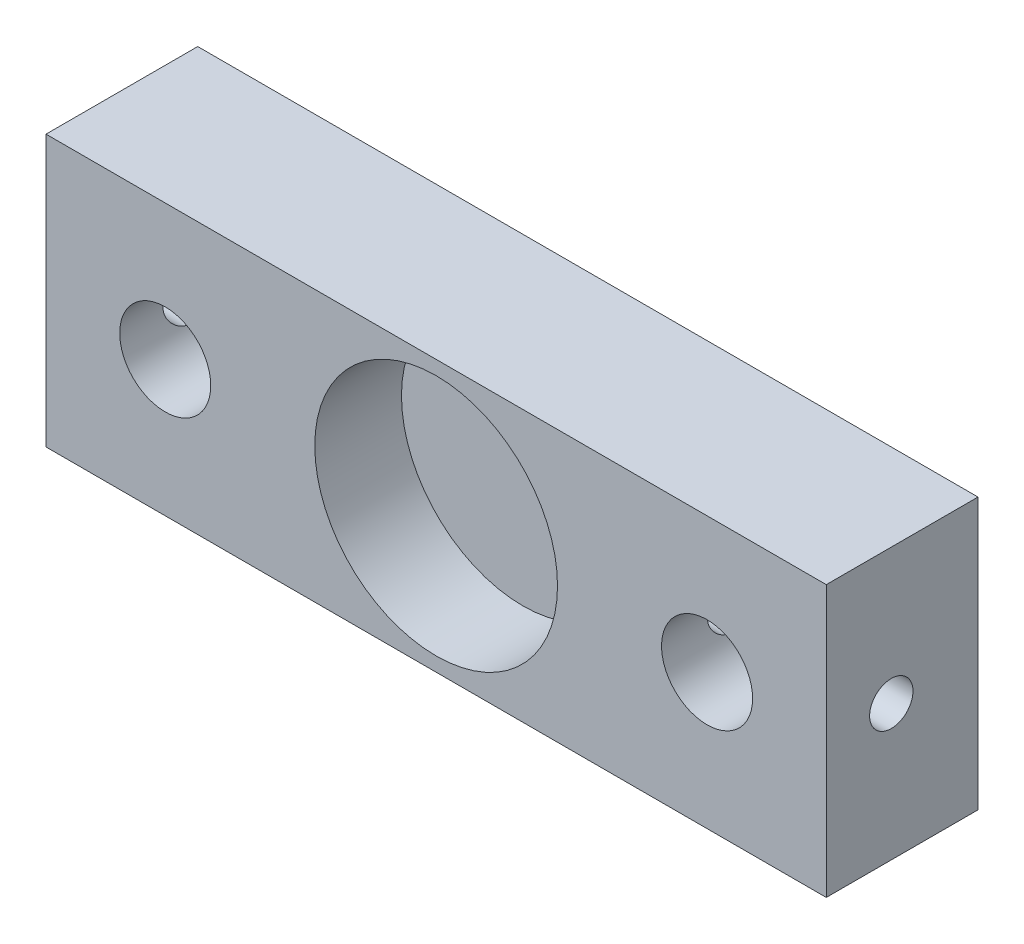
SolidWorks part; units mm, degrees
ref_plane "Płaszczyzna przednia" through (0, 0, 0) normal (0, 0, 1) x (1, 0, 0)
ref_plane "Płaszczyzna górna" through (0, 0, 0) normal (0, 1, 0) x (1, 0, 0)
ref_plane "Płaszczyzna prawa" through (0, 0, 0) normal (1, 0, 0) x (0, 0, -1)
sketch "Sketch1" plane through (0, 0, 0) normal (0, 0, 1) x (1, 0, 0)
  line L1 (-36, 12.5) -> (36, 12.5)
  line L2 (-36, 12.5) -> (-36, -12.5)
  line L3 (-36, -12.5) -> (36, -12.5)
  line L4 (36, 12.5) -> (36, -12.5)
  line L5 (-36, 12.5) -> (36, -12.5) construction
  line L6 (-36, -12.5) -> (36, 12.5) construction
  point P4 (0, 0)
  point P140 (0, 0)
  dimension "D1" = 72
  dimension "D2" = 25
extrude "Boss-Extrude1" add sketch "Sketch1" along normal blind 14
sketch "Sketch2" plane through (0, 0, 14) normal (0, 0, 1) x (1, 0, 0)
  circle A0 centre (0, 0) radius 11.2
  point P0 (0, 0)
  dimension "D1" = 22.4
extrude "Cut-Extrude1" cut sketch "Sketch2" against normal blind 8
sketch "Sketch3" plane through (0, 0, 14) normal (0, 0, 1) x (1, 0, 0)
  line L0 (-36, 0) -> (36, 0) construction
  line L1 (-36, 12.5) -> (-36, -12.5) construction
  line L2 (36, -12.5) -> (36, 12.5) construction
  circle A0 centre (-25, 0) radius 4.2
  circle A1 centre (25, 0) radius 4.2
  dimension "D3" = 8.4
  dimension "D4" = 8.4
  dimension "D1" = 25
  dimension "D2" = 25
extrude "Cut-Extrude2" cut sketch "Sketch3" against normal blind 12
sketch "Sketch4" plane through (-36, 0, 0) normal (-1, 0, 0) x (0, 0, 1)
  line L0 (0, 0) -> (14, 0) construction
  line L1 (0, 12.5) -> (0, -12.5) construction
  line L2 (14, 12.5) -> (14, -12.5) construction
  circle A0 centre (8, 0) radius 1.5
  point P6 (8, 0)
  dimension "D2" = 3
  dimension "D1" = 6
hole_wizard "Ø3.5 (3.5) Diameter Hole1" positions "Sketch4" profile "Sketch5" hole size "Ø3.5" standard "DIN"
sketch "Sketch5" plane through (-36, 0, 8) normal (0, 1, 0) x (0, 0, 1)
  line L0 (0, 0) -> (0, 21.0515)
  line L1 (0, 21.0515) -> (1.75, 20)
  line L2 (1.75, 20) -> (1.75, 0)
  line L5 (1.75, 0) -> (0, 0)
  line L10 (0, 21.0515) -> (-1.75, 20) construction
  line L11 (0, -6.35) -> (0, 107.95) construction
  dimension "Hole Dia." = 3.5
  dimension "Hole Depth" = 20
  dimension "Drill Angle" = 118
sketch "Sketch6" plane through (-36, 0, 0) normal (-1, 0, 0) x (0, 0, 1)
  circle A0 centre (8, 0) radius 2
  dimension "D1" = 4
extrude "Cut-Extrude3" cut sketch "Sketch6" against normal up to next
mirror "Mirror1" about plane through (0, 0, 0) normal (1, 0, 0) of "Ø3.5 (3.5) Diameter Hole1", "Cut-Extrude3"
